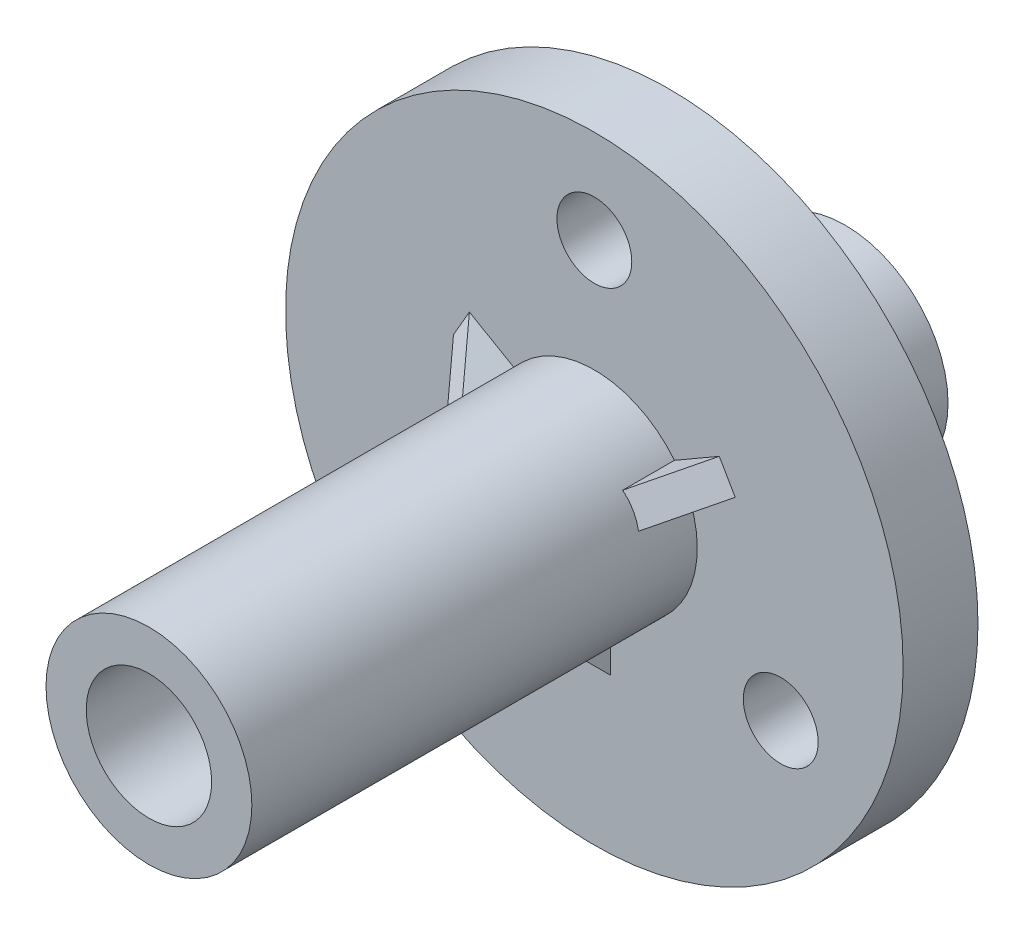
SolidWorks part; units mm, degrees
ref_plane "Alzado" through (0, 0, 0) normal (0, 0, 1) x (1, 0, 0)
ref_plane "Planta" through (0, 0, 0) normal (0, 1, 0) x (1, 0, 0)
ref_plane "Vista lateral" through (0, 0, 0) normal (1, 0, 0) x (0, 0, -1)
sketch "Croquis1" plane through (0, 0, 0) normal (0, 0, 1) x (1, 0, 0)
  line L0 (0, 11.5) -> (0, 0) construction
  line L1 (0, 0) -> (-9.9593, -5.75) construction
  line L2 (0, 0) -> (9.9593, -5.75) construction
  circle A0 centre (0, 0) radius 16.5
  circle A1 centre (0, 11.5) radius 2
  circle A2 centre (0, 0) radius 11.5 construction
  circle A3 centre (-9.9593, -5.75) radius 2
  circle A4 centre (9.9593, -5.75) radius 2
  point P10 (0, 16.5)
  point P11 (0, 13.5)
  dimension "D3" = 4
  dimension "D4" = 33
  dimension "D5" = 3
  dimension "D1" = 120
  dimension "D2" = 120
extrude "Saliente-Extruir1" add sketch "Croquis1" along normal blind 4
sketch "Croquis2" plane through (0, 0, 4) normal (0, 0, 1) x (1, 0, 0)
  circle A0 centre (0, 0) radius 5.5
  dimension "D1" = 11
extrude "Saliente-Extruir2" add sketch "Croquis2" along normal blind 23.8
sketch "Croquis3" plane through (0, 0, 0) normal (0, 0, -1) x (-1, 0, 0)
  circle A0 centre (0, 0) radius 5.5
  dimension "D1" = 11
extrude "Saliente-Extruir3" add sketch "Croquis3" along normal blind 9.4
sketch "Croquis5" plane through (0, 0, 27.8) normal (0, 0, 1) x (1, 0, 0)
  circle A0 centre (0, 0) radius 3.35
  dimension "D1" = 6.7
extrude "Cortar-Extruir1" cut sketch "Croquis5" against normal up to surface (37.2 mm away) up to face at (-5.5, 0, -9.4)
sketch "Croquis7" plane through (0, 0, 0) normal (1, 0, 0) x (0, 0, -1)
  line L0 (-4, -5.5) -> (-6.7, -5.5)
  line L1 (-27.8, -5.5) -> (-4, -5.5) construction
  line L2 (-6.7, -5.5) -> (-4, -8.2)
  line L3 (-4, -8.2) -> (-4, -5.5)
  line L4 (-6.7, -5.5) -> (-7.3253, -4.8747)
  line L5 (-7.3253, -4.8747) -> (-4, -4.8747)
  line L6 (-4, -4.8747) -> (-4, -5.5)
  line L7 (-4, 16.5) -> (-4, -16.5) construction
  line L8 (-4, 16.5) -> (-4, -16.5) construction
  dimension "D1" = 8.3
extrude "Saliente-Extruir7" add sketch "Croquis7" along normal blind 0.85 and the other way blind 0.85 contours L6 L5 L4 L0 | L2 L3 L0 region at (0, -6.4, 4.9) region at (0, -5.1765, 5.5117)
pattern_circular "MatrizC1" count 3 over 360 about axis through (0, 0, -18.8752) along (0, 0, 1) of "Saliente-Extruir7"
ref_plane "Plano3" through (0, 0, 2) normal (0, 0, 1) x (1, 0, 0)
mirror "Simetría1" about plane through (0, 0, 2) normal (0, 0, 1) of "MatrizC1"
